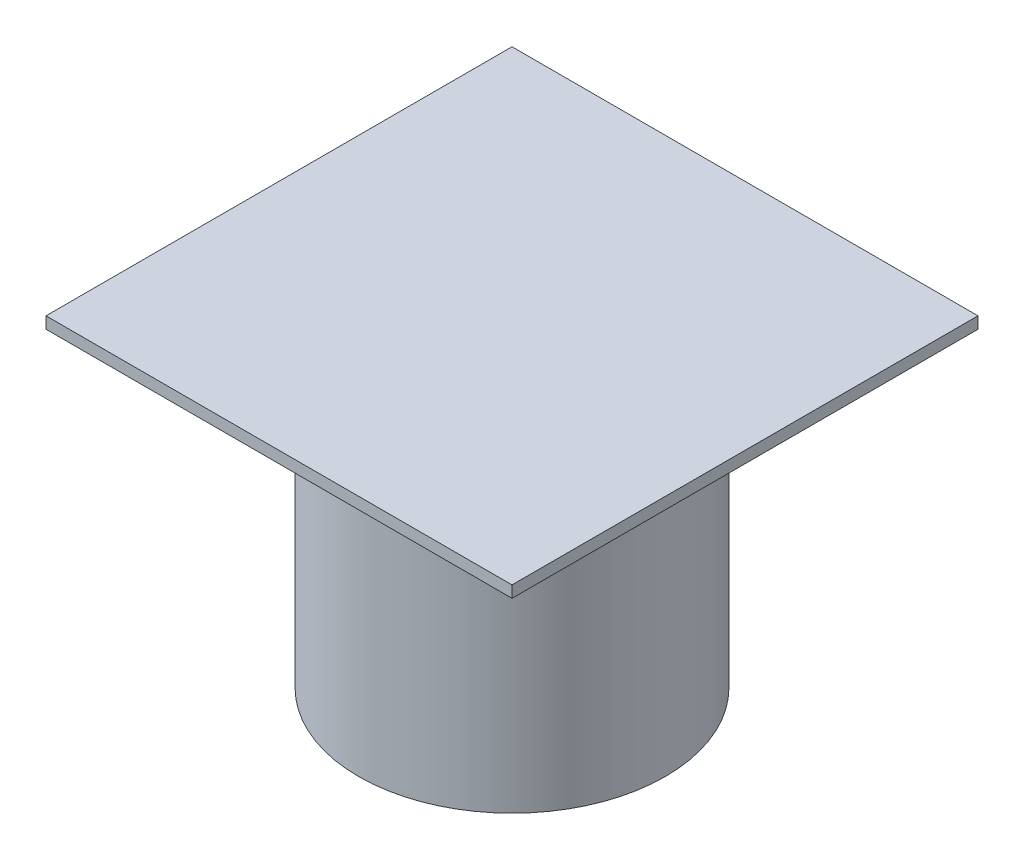
SolidWorks part; units mm, degrees
ref_plane "Front Plane" through (0, 0, 0) normal (0, 0, 1) x (1, 0, 0)
ref_plane "Top Plane" through (0, 0, 0) normal (0, 1, 0) x (1, 0, 0)
ref_plane "Right Plane" through (0, 0, 0) normal (1, 0, 0) x (0, 0, -1)
sketch "Sketch1" plane through (0, 0, 0) normal (0, 1, 0) x (1, 0, 0)
  circle A0 centre (0, 0) radius 39.5
extrude "Boss-Extrude1" add sketch "Sketch1" along normal blind 80
sketch "Sketch2" plane through (0, 80, 0) normal (0, 1, 0) x (1, 0, 0)
  line L0 (60, 60) -> (-60, 60)
  line L1 (60, 60) -> (60, -60)
  line L2 (-60, 60) -> (-60, -60)
  line L3 (60, -60) -> (-60, -60)
  line L4 (60, 60) -> (-60, -60) construction
  line L5 (-60, 60) -> (60, -60) construction
  point P1 (0, 0)
  dimension "D1" = 120
  dimension "D2" = 120
extrude "Boss-Extrude2" add sketch "Sketch2" along normal blind 3
